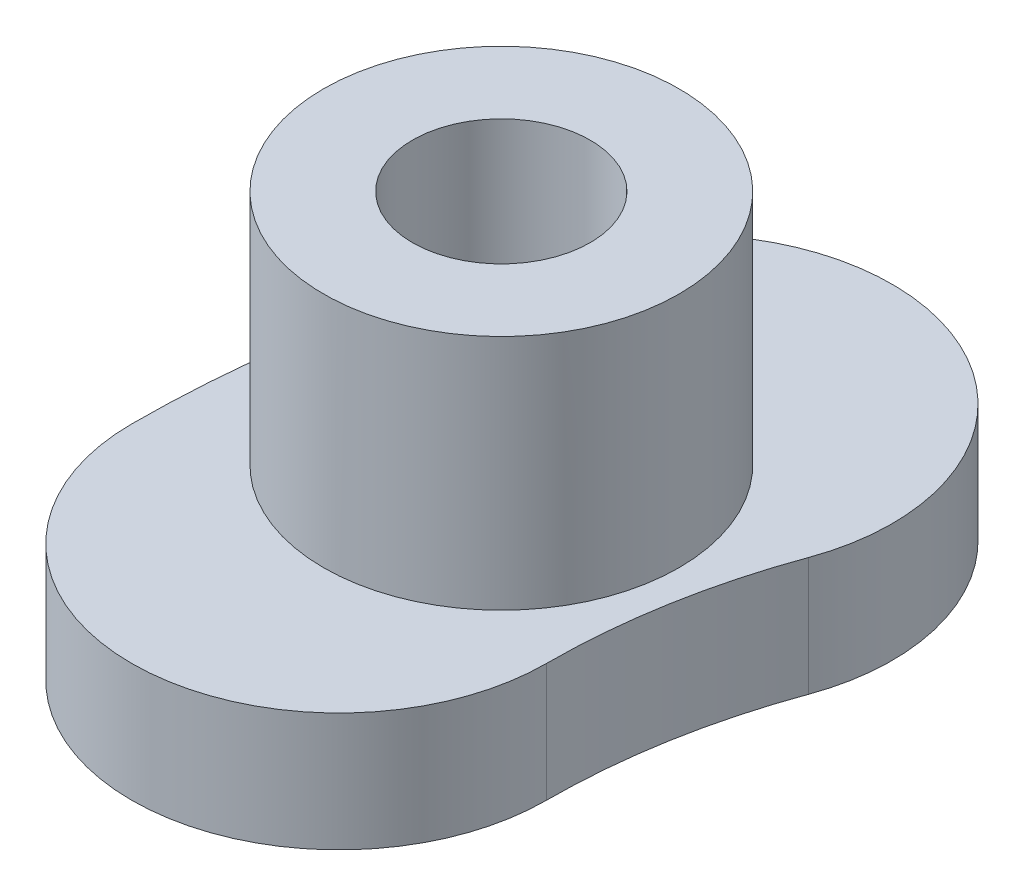
SolidWorks part; units mm, degrees
note: The reader was unsure of these and kept them because the rebuilt part matched: shared geometry of "草图2<3>".
ref_plane "前视基准面" through (0, 0, 0) normal (0, 0, 1) x (1, 0, 0)
ref_plane "上视基准面" through (0, 0, 0) normal (0, 1, 0) x (1, 0, 0)
ref_plane "右视基准面" through (0, 0, 0) normal (1, 0, 0) x (0, 0, -1)
sketch "草图2" plane through (0, 0, 0) normal (0, 1, 0) x (1, 0, 0)
  line L0 (-14.5, 0) -> (0, 0) construction
  line L1 (0, 0) -> (-13.6255, 4.9593) construction
  arc A0 (-14.5, 0) -> (-13.6255, 4.9593) centre (0, 0) cw construction
  arc A1 (-16.9145, 6.1564) -> (-18, 0) centre (0, 0) ccw
  arc A2 (-10.3366, 3.7622) -> (-11, 0) centre (0, 0) ccw
  arc A3 (-10.3366, 3.7622) -> (-16.9145, 6.1564) centre (-13.6255, 4.9593) ccw
  arc A4 (-18, 0) -> (-11, 0) centre (-14.5, 0) ccw
  circle A5 centre (-14.2797, 2.5179) radius 1.5
  point P3 (-14.2797, 2.5179)
  dimension "D1" = 14.5
  dimension "D3" = 11
  dimension "D4" = 3
  dimension "D2" = 20
extrude "凸台-拉伸1" add sketch "草图2" along normal blind 2 contours A1 A4 A2 A3 A5
extrude "拉伸-薄壁1" add sketch "草图2<3>" along normal blind 6 thin contours A5
sketch "草图2<3>" plane through (0, 0, 0) normal (0, 1, 0) x (1, 0, 0) same geometry as "草图2"
equation "\"D3@草图2\"=\"D1@草图2\"-3.5"
